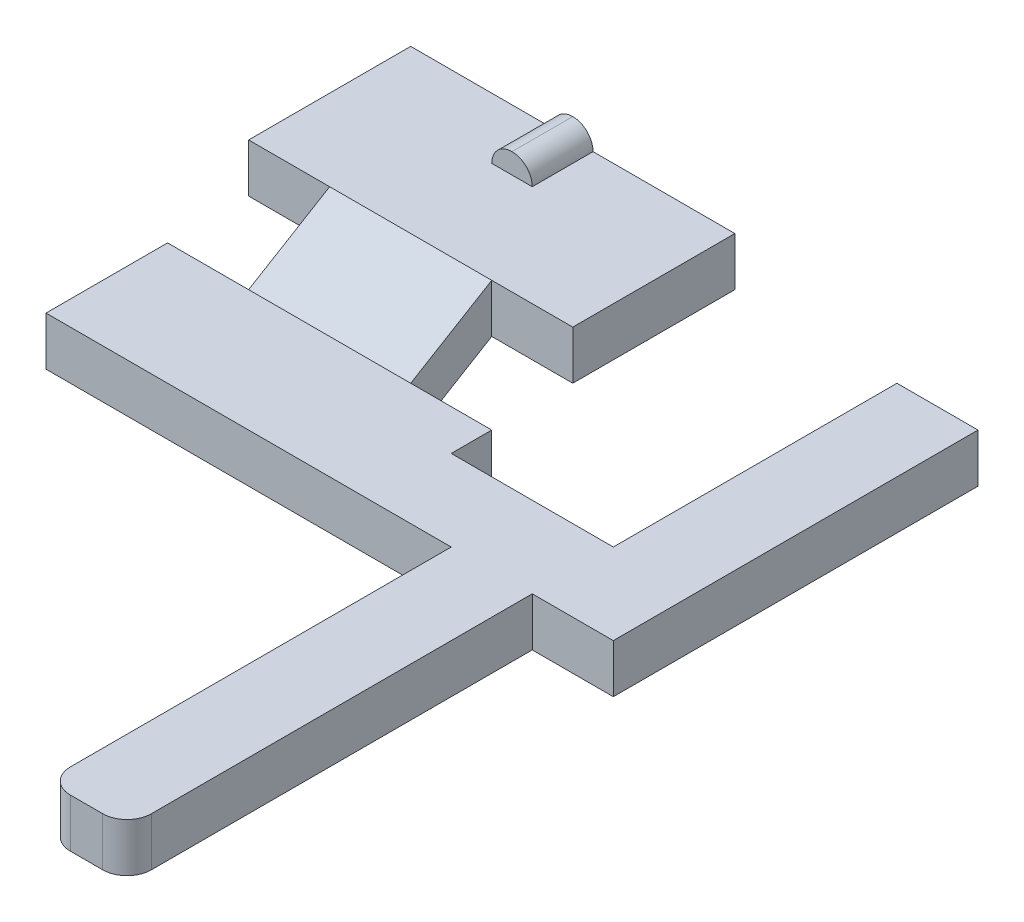
SolidWorks part; units mm, degrees
ref_plane "Front Plane" through (0, 0, 0) normal (0, 0, 1) x (1, 0, 0)
ref_plane "Top Plane" through (0, 0, 0) normal (0, 1, 0) x (1, 0, 0)
ref_plane "Right Plane" through (0, 0, 0) normal (1, 0, 0) x (0, 0, -1)
sketch "Sketch1" plane through (0, 0, 0) normal (0, 1, 0) x (1, 0, 0)
  line L0 (0, 0) -> (0, 5)
  line L1 (0, 5) -> (1, 5)
  line L2 (1, 5) -> (1, 9.5)
  line L3 (1, 9.5) -> (0, 9.5)
  line L4 (0, 9.5) -> (0, 6)
  line L5 (0, 6) -> (-2, 6)
  line L6 (-2, 6) -> (-2, 6.5)
  line L7 (-2, 6.5) -> (-6, 6.5)
  line L8 (-6, 6.5) -> (-6, 5)
  line L9 (-6, 5) -> (-1, 5)
  line L10 (-1, 5) -> (-1, 0)
  line L11 (-1, 0) -> (0, 0)
  dimension "D1" = 5
  dimension "D2" = 4.5
  dimension "D3" = 4
  dimension "D4" = 0.5
  dimension "D5" = 5
  dimension "D6" = 2
  dimension "D7" = 1
  dimension "D8" = 1.5
extrude "Boss-Extrude1" add sketch "Sketch1" along normal blind 0.6
sketch "Sketch2" plane through (0, 0.6, 0) normal (0, 1, 0) x (1, 0, 0)
  line L2 (-6, 9.5) -> (-2, 9.5)
  line L3 (-6, 9.5) -> (-6, 7.5)
  line L4 (-6, 7.5) -> (-2, 7.5)
  line L5 (-2, 9.5) -> (-2, 7.5)
  dimension "D1" = 3
  dimension "D2" = 2
  dimension "D3" = 4
  dimension "D4" = 7
extrude "Boss-Extrude2" add sketch "Sketch2" along normal blind 0.6 separate body
sketch "Sketch3" plane through (0, 0, -7.5) normal (0, 0, 1) x (1, 0, 0)
  line L0 (-6, 1.2) -> (-2, 1.2) construction
  line L1 (-3, 1.2) -> (-5, 1.2)
  line L2 (-3, 1.2) -> (-3, 0.6)
  line L3 (-3, 0.6) -> (-5, 0.6)
  line L4 (-5, 1.2) -> (-5, 0.6)
  line L5 (-6, 0.6) -> (-2, 0.6) construction
  dimension "D1" = 2
  dimension "D2" = 1
sketch "Sketch4" plane through (0, 0, -6.5) normal (0, 0, -1) x (-1, 0, 0)
  line L0 (2, 0.6) -> (6, 0.6) construction
  line L1 (3, 0.6) -> (5, 0.6)
  line L2 (3, 0.6) -> (3, 0)
  line L3 (3, 0) -> (5, 0)
  line L4 (5, 0.6) -> (5, 0)
  line L5 (2, 0) -> (6, 0) construction
  dimension "D1" = 2
  dimension "D2" = 1
loft "Loft1" add profiles "Sketch3", "Sketch4" connector at (-5, 1.2, -7.5) connector at (-5, 0.6, -6.5)
fillet "Fillet1" radius 0.3 2 edges at (-1, 0.3, 0) (0, 0.3, 0)
sketch "Sketch5" plane through (0, 1.2, 0) normal (0, 1, 0) x (1, 0, 0)
  line L0 (-2, 9.5) -> (-6, 9.5) construction
  line L1 (-3.75, 9.5) -> (-4.25, 9.5)
  line L2 (-3.75, 9.5) -> (-3.75, 8.75)
  line L3 (-3.75, 8.75) -> (-4.25, 8.75)
  line L4 (-4.25, 9.5) -> (-4.25, 8.75)
  dimension "D1" = 0.5
  dimension "D2" = 0.75
  dimension "D3" = 1.75
extrude "Boss-Extrude3" add sketch "Sketch5" along normal blind 0.25
fillet "Fillet2" radius 0.25 2 edges at (-3.75, 1.45, -9.125) (-4.25, 1.45, -9.125)
